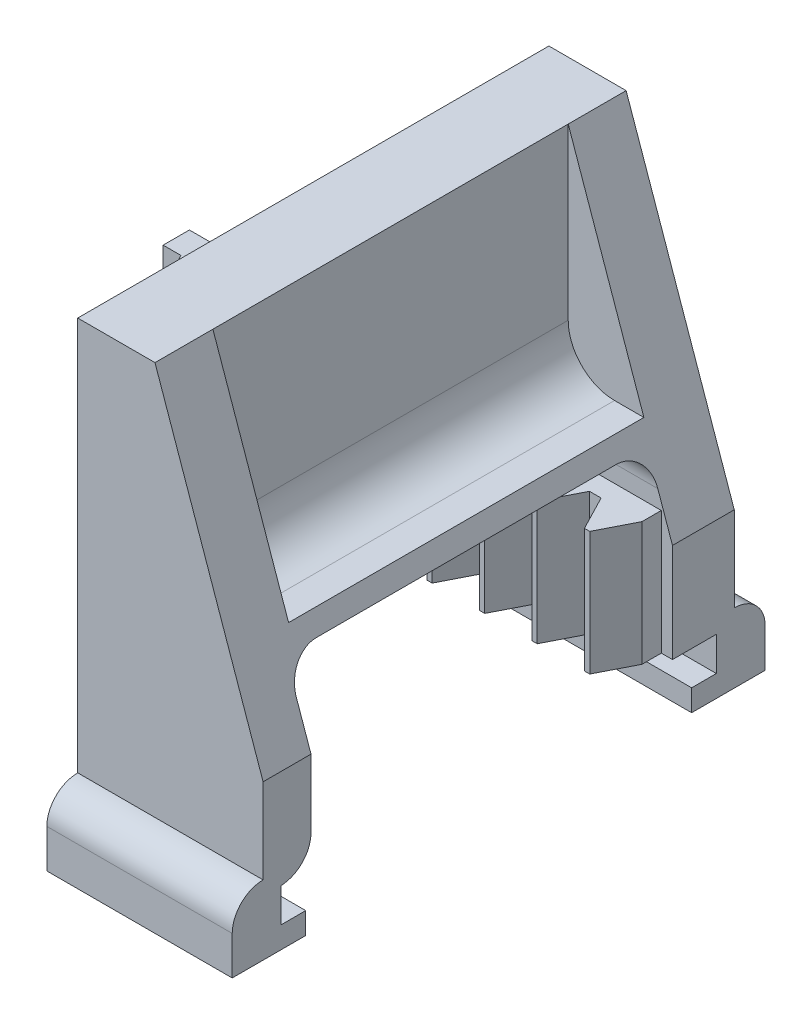
SolidWorks part; units mm, degrees
ref_plane "Front Plane" through (0, 0, 0) normal (0, 0, 1) x (1, 0, 0)
ref_plane "Top Plane" through (0, 0, 0) normal (0, 1, 0) x (1, 0, 0)
ref_plane "Right Plane" through (0, 0, 0) normal (1, 0, 0) x (0, 0, -1)
sketch "Sketch1" plane through (0, 0, 0) normal (0, 0, 1) x (1, 0, 0)
  line L0 (0, 0) -> (0, -30)
  line L1 (0, -30) -> (12, -30)
  line L2 (12, -30) -> (12, -20)
  line L3 (12, -20) -> (5, 0)
  line L4 (5, 0) -> (0, 0)
  dimension "D1" = 30
  dimension "D2" = 12
  dimension "D3" = 10
  dimension "D4" = 5
extrude "Boss-Extrude1" add sketch "Sketch1" against normal blind 30.5
sketch "Sketch4" plane through (0, 0, 0) normal (-1, 0, 0) x (0, 0, 1)
  line L0 (-30.5, 0) -> (-30.5, -30) construction
  line L1 (-26.5, -15.288) -> (-3.1, -15.288)
  line L2 (-26.5, -15.288) -> (-26.5, -30.288)
  line L3 (-26.5, -30.288) -> (-3.1, -30.288)
  line L4 (-3.1, -15.288) -> (-3.1, -30.288)
  point P4 (-26.5, -22.788)
  dimension "D1" = 23.4
  dimension "D2" = 15
  dimension "D3" = 4
extrude "Cut-Extrude2" cut sketch "Sketch4" against normal blind 25 contours L2 L1 L4 L3
ref_plane "Plane1" through (0, 0, -15.25) normal (0, 0, 1) x (1, 0, 0)
sketch "Sketch6" plane through (0, 0, -15.25) normal (0, 0, 1) x (1, 0, 0)
  line L0 (5, 0) -> (5, -14)
  line L1 (5, -14) -> (9.9, -14)
  line L2 (12, -20) -> (5, 0) construction
  line L3 (9.9, -14) -> (5, 0)
  dimension "D1" = 14
extrude "Cut-Extrude4" cut sketch "Sketch6" against normal mid plane 23
ref_plane "Plane2" through (0, -26.4, 0) normal (0, 1, 0) x (1, 0, 0)
sketch "Sketch7" plane through (0, -26.4, 0) normal (0, 1, 0) x (1, 0, 0)
  line L0 (11.2768, 26.95) -> (-19.7232, 26.95)
  line L62 (-6.6, 15.25) -> (6.6, 15.25) construction
  line L162 (11.2768, 26.95) -> (11.2768, 25.25)
  line L172 (-19.7232, 25.25) -> (-19.7232, 26.95)
  line L243 (11.2768, 25.25) -> (-19.7232, 25.25)
  dimension "D2" = 31
  dimension "D3" = 1.7
  dimension "D7" = 11.7
sketch "Sketch9" plane through (0, 0, 0) normal (-1, 0, 0) x (0, 0, 1)
  line L0 (-6.1597, -26.4) -> (-1.1597, -26.4)
  line L2 (-1.1597, -26.4) -> (-1.1597, -28.6)
  line L3 (-1.1597, -28.6) -> (-2.7597, -28.6)
  line L4 (-2.7597, -28.6) -> (-2.7597, -30.2967)
  line L5 (-2.7597, -30.2967) -> (-6.1597, -30.2967)
  line L6 (-6.1597, -30.2967) -> (-6.1597, -26.4)
  line L7 (-3.1, -30) -> (0, -30) construction
  line L15 (-15.25, -16.5) -> (-15.25, 16.5) construction
  line L16 (-27.7403, -30.2967) -> (-24.3403, -30.2967)
  line L17 (-27.7403, -28.6) -> (-27.7403, -30.2967)
  line L18 (-29.3403, -28.6) -> (-27.7403, -28.6)
  line L19 (-29.3403, -26.4) -> (-29.3403, -28.6)
  line L20 (-24.3403, -26.4) -> (-29.3403, -26.4)
  line L21 (-24.3403, -30.2967) -> (-24.3403, -26.4)
  dimension "D1" = 5
  dimension "D2" = 2.2
  dimension "D3" = 1.4
  dimension "D4" = 1.6
extrude "Boss-Extrude3" add sketch "Sketch7" along normal blind 8
sketch "Sketch10" plane through (0, -18.4, 0) normal (0, 1, 0) x (1, 0, 0)
  line L0 (11.2768, 25.25) -> (10.1347, 23.0104)
  line L2 (10.1347, 23.0104) -> (9.7913, 23.0104)
  line L3 (9.7913, 23.0104) -> (8.6309, 25.25)
  line L4 (-19.7232, 25.25) -> (11.2768, 25.25) construction
  line L5 (8.6309, 25.25) -> (11.2768, 25.25)
extrude "Boss-Extrude4" add sketch "Sketch10" against normal up to vertex (8 mm away) up to point (-19.7232, -26.4, -25.25)
pattern_linear "LPattern1" count 9 spacing 3.4 along (-1, 0, 0) of "Boss-Extrude4"
sketch "Sketch11" plane through (0, 0, -30.5) normal (0, 0, -1) x (-1, 0, 0)
  line L0 (-12, -30) -> (-12, -20) construction
  line L1 (-12, -25.5) -> (0, -25.5)
  line L2 (-12, -25.5) -> (-12, -30)
  line L3 (-12, -30) -> (0, -30)
  line L4 (0, -25.5) -> (0, -30)
  dimension "D1" = 4.5
extrude "Boss-Extrude5" add sketch "Sketch11" along normal blind 2
fillet "Fillet1" radius 2 1 edges at (6, -25.5, -32.5)
mirror "Mirror1" about plane through (0, 0, -15.25) normal (0, 0, 1) of "Boss-Extrude5"
fillet "Fillet2" radius 2 1 edges at (6, -25.5, 2)
extrude "Cut-Extrude5" cut sketch "Sketch9" against normal through all
fillet "Fillet4" radius 2 3 edges at (5.1754, -15.288, -3.1) (5.1754, -15.288, -26.5) (6, -26.4, -3.1)
fillet "Fillet5" radius 3 1 edges at (5, -14, -15.25)
